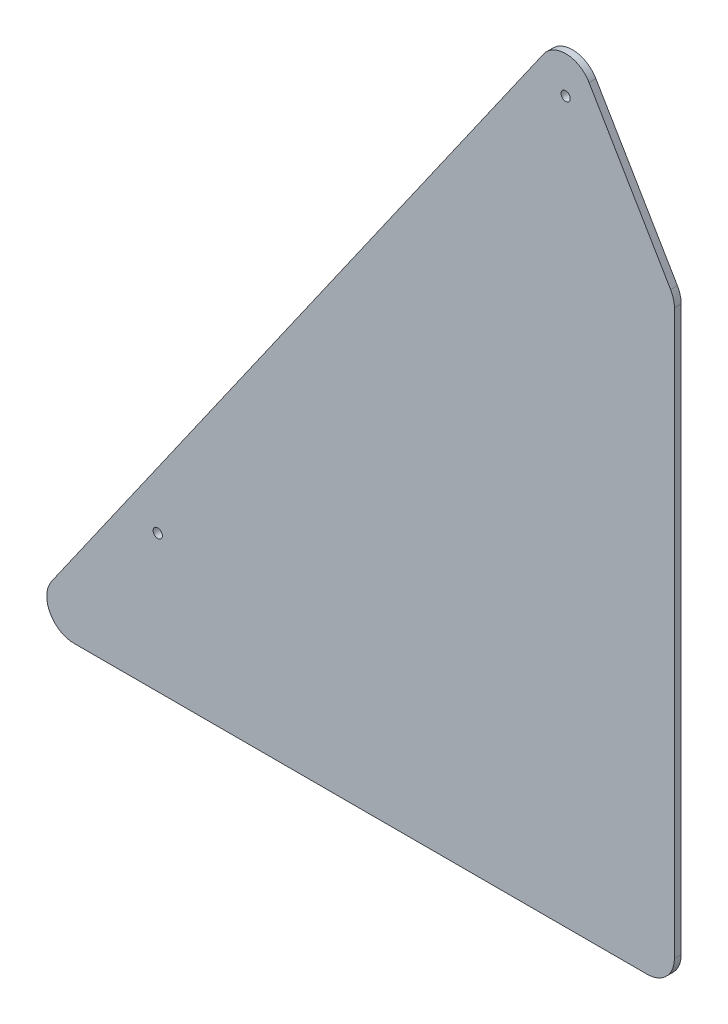
SolidWorks part; units mm, degrees
ref_plane "Front Plane" through (0, 0, 0) normal (0, 0, 1) x (1, 0, 0)
ref_plane "Top Plane" through (0, 0, 0) normal (0, 1, 0) x (1, 0, 0)
ref_plane "Right Plane" through (0, 0, 0) normal (1, 0, 0) x (0, 0, -1)
sketch "Sketch1" plane through (0, 0, 0) normal (0, 0, 1) x (1, 0, 0)
  line L0 (0, 0) -> (304.8, 0)
  line L1 (304.8, 0) -> (304.8, 279.4)
  line L2 (254.9547, 364.1131) -> (0, 0)
  line L3 (304.8, 279.4) -> (254.9547, 364.1131)
  point P9 (0, 0)
  dimension "D1" = 304.8
  dimension "D2" = 279.4
  dimension "D3" = 55
  dimension "D4" = 444.5
extrude "Boss-Extrude1" add sketch "Sketch1" along normal blind 3.175
sketch "Sketch2" plane through (0, 0, 3.175) normal (0, 0, 1) x (1, 0, 0)
  line L0 (254.9547, 364.1131) -> (0, 0) construction
  circle A0 centre (63.5, 64.1173) radius 2.159
  circle A1 centre (254, 336.1795) radius 2.159
  dimension "D3" = 4.318
  dimension "D5" = 4.318
  dimension "D1" = 63.5
  dimension "D2" = 15.24
  dimension "D4" = 254
  dimension "D6" = 15.24
extrude "Cut-Extrude1" cut sketch "Sketch2" against normal through all
fillet "Fillet1" radius 12.7 4 edges at (0, 0, 1.5875) (304.8, 0, 1.5875) (304.8, 279.4, 1.5875) (254.9547, 364.1131, 1.5875)
equation "\"D6@Sketch2\"=\"D2@Sketch2\""
